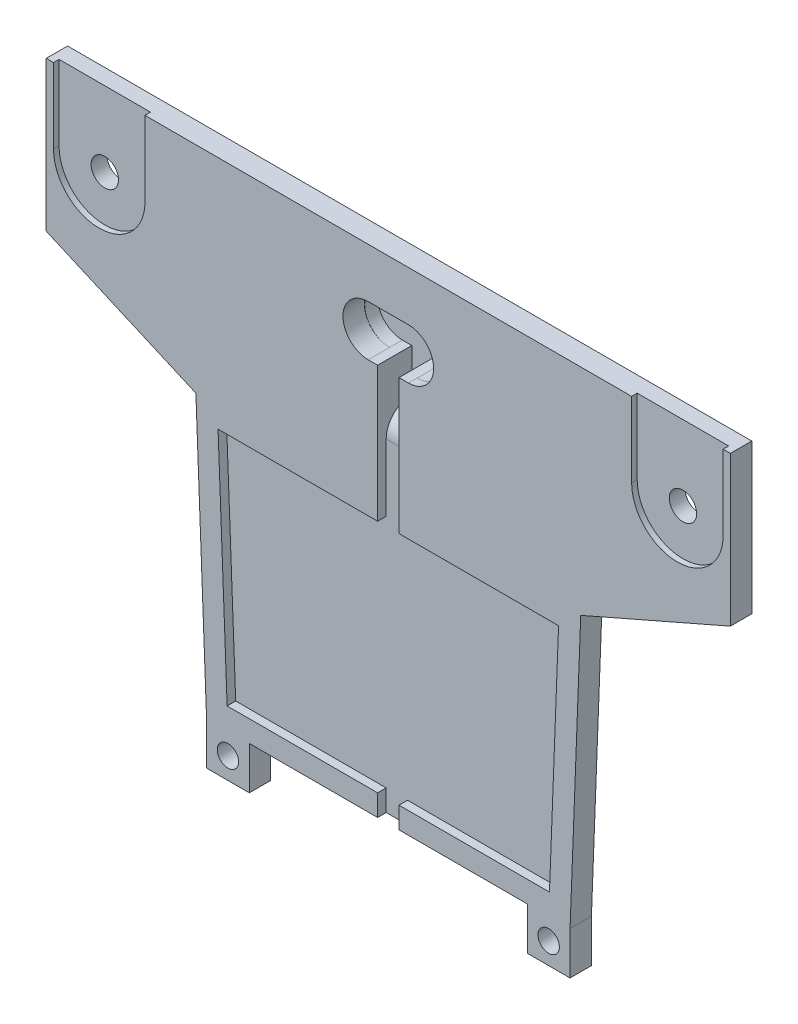
SolidWorks part; units mm, degrees
ref_plane "Front Plane" through (0, 0, 0) normal (0, 0, 1) x (1, 0, 0)
ref_plane "Top Plane" through (0, 0, 0) normal (0, 1, 0) x (1, 0, 0)
ref_plane "Right Plane" through (0, 0, 0) normal (1, 0, 0) x (0, 0, -1)
sketch "Sketch1" plane through (0, 0, 0) normal (0, 0, 1) x (1, 0, 0)
  line L0 (-53.975, 0) -> (53.975, 0)
  line L1 (53.975, 0) -> (57.15, 82.1613)
  line L2 (57.15, 82.1613) -> (101.6, 101.6)
  line L3 (101.6, 101.6) -> (101.6, 146.05)
  line L4 (101.6, 146.05) -> (-101.6, 146.05)
  line L5 (-101.6, 146.05) -> (-101.6, 101.6)
  line L6 (-101.6, 101.6) -> (-57.15, 82.1613)
  line L7 (-57.15, 82.1613) -> (-53.975, 0)
  point P4 (0, 0)
  point P5 (0, 0)
  point P11 (0, 146.05)
  dimension "D1" = 44.45
  dimension "D2" = 44.45
  dimension "D3" = 146.05
  dimension "D4" = 107.95
  dimension "D5" = 203.2
  dimension "D6" = 114.3
base flange "Main Body" sketch "Sketch1" thickness 6.35 reverse thickness direction no parameters "D1"=1
sketch "Sketch7" plane through (0, 0, 0) normal (0, 0, 1) x (1, 0, 0)
  line L0 (-50.5649, 76.2) -> (-47.8656, 6.35)
  line L1 (-47.8656, 6.35) -> (47.8656, 6.35)
  line L2 (47.8656, 6.35) -> (50.5649, 76.2)
  line L3 (50.5649, 76.2) -> (-50.5649, 76.2)
  line L4 (-57.15, 82.1613) -> (-53.975, 0) construction
  line L8 (-53.975, 0) -> (53.975, 0) construction
  line L9 (53.975, 0) -> (57.15, 82.1613) construction
  point P2 (0, 6.35)
  point P5 (0, 76.2)
  dimension "D1" = 6.35
  dimension "D2" = 6.35
  dimension "D3" = 69.85
  dimension "D4" = 6.35
extrude "Battery Spacing" cut sketch "Sketch7" against normal blind 2.54 normal cut yes
sketch "Sketch8" plane through (0, 0, 0) normal (0, 0, 1) x (1, 0, 0)
  line L0 (-5.969, 131.318) -> (5.969, 131.318)
  line L1 (5.969, 116.332) -> (-5.969, 116.332)
  line L3 (101.6, 146.05) -> (-101.6, 146.05) construction
  arc A0 (5.969, 131.318) -> (5.969, 116.332) centre (5.969, 123.825) cw
  arc A1 (-5.969, 116.332) -> (-5.969, 131.318) centre (-5.969, 123.825) cw
  circle A2 centre (85.852, 123.825) radius 4.064
  circle A3 centre (-85.852, 123.825) radius 4.064
  point P5 (1.524, 123.825)
  point P7 (-1.524, 123.825)
  point P8 (0, 131.318)
  point P9 (0, 116.332)
  point P12 (-13.462, 123.825)
  point P13 (13.462, 123.825)
  point P21 (0, 146.05)
  dimension "D1" = 26.924
  dimension "D2" = 72.39
  dimension "D3" = 72.39
  dimension "D4" = 14.732
  dimension "D5" = 11.938
extrude "Light Sockets" cut sketch "Sketch8" against normal blind 12.7 normal cut yes
sketch "Sketch9" plane through (0, 0, -6.35) normal (0, 0, -1) x (-1, 0, 0)
  line L0 (-9.525, 111.7653) -> (-9.525, 99.0653)
  line L1 (-9.525, 99.0653) -> (9.525, 99.0653)
  line L2 (9.525, 99.0653) -> (9.525, 111.7653)
  line L3 (9.525, 111.7653) -> (9.1017, 112.1697)
  line L4 (5.969, 136.398) -> (-5.969, 136.398)
  line L5 (-5.969, 111.252) -> (5.969, 111.252)
  line L6 (5.969, 136.398) -> (-5.969, 136.398)
  arc A4 (5.969, 111.252) -> (5.969, 136.398) centre (5.969, 123.825) ccw
  arc A5 (-5.969, 136.398) -> (-5.969, 111.252) centre (-5.969, 123.825) ccw
  arc A6 (9.525, 111.7653) -> (5.969, 136.398) centre (5.969, 123.825) ccw
  arc A7 (-5.969, 136.398) -> (-9.525, 111.7653) centre (-5.969, 123.825) ccw
  dimension "D2" = 19.05
  dimension "D3" = 12.7
  dimension "D4" = 12.7
  dimension "D1" = 5.08
extrude "Light Leads Pocket" add sketch "Sketch9" along normal blind 6.35
sketch "Sketch10" plane through (0, 0, 0) normal (0, 0, 1) x (1, 0, 0)
  line L0 (-3.175, 116.332) -> (3.175, 116.332)
  line L1 (-5.969, 116.332) -> (5.969, 116.332) construction
  line L2 (-5.969, 116.332) -> (5.969, 116.332) construction
  line L3 (3.175, 116.332) -> (3.175, 76.2)
  line L4 (50.5649, 76.2) -> (-50.5649, 76.2) construction
  line L5 (3.175, 76.2) -> (3.175, 6.35)
  line L6 (-47.8656, 6.35) -> (47.8656, 6.35) construction
  line L7 (3.175, 6.35) -> (3.175, 0)
  line L8 (-53.975, 0) -> (53.975, 0) construction
  line L9 (3.175, 0) -> (-3.175, 0)
  line L10 (-3.175, 0) -> (-3.175, 116.332)
  point P6 (0, 116.332)
  dimension "D1" = 6.35
extrude "Wire Trail" cut sketch "Sketch10" against normal blind 2.54 normal cut yes
sketch "Sketch12" plane through (0, 0, -2.54) normal (0, 0, 1) x (1, 0, 0)
  line L0 (-3.175, 116.332) -> (-5.9601, 116.332)
  line L1 (3.175, 116.332) -> (3.175, 103.7305)
  line L2 (3.175, 76.2) -> (3.175, 116.332) construction
  line L3 (3.175, 103.7305) -> (-3.175, 103.7305)
  line L4 (-3.175, 116.332) -> (-3.175, 76.2) construction
  line L5 (-3.175, 103.7305) -> (-3.175, 116.332)
  line L6 (-3.175, 116.332) -> (-3.175, 76.2) construction
  line L7 (3.175, 76.2) -> (3.175, 116.332) construction
  line L8 (-5.9601, 131.1354) -> (6.0002, 131.1354)
  line L9 (6.0002, 116.332) -> (3.175, 116.332)
  arc A0 (-5.9601, 116.332) -> (-5.9601, 131.1354) centre (-5.9601, 123.7337) cw
  arc A1 (6.0002, 131.1354) -> (6.0002, 116.332) centre (6.0002, 123.7337) cw
extrude "Lead Room" cut sketch "Sketch12" against normal blind 7.62 normal cut yes
fillet "Fillet1" radius 7.62 1 edges at (0, 103.7305, -2.54)
sketch "Sketch13" plane through (0, 0, 0) normal (0, 0, 1) x (1, 0, 0)
  line L0 (72.263, 146.05) -> (72.263, 123.825)
  line L1 (101.6, 146.05) -> (-101.6, 146.05) construction
  line L2 (99.441, 123.825) -> (99.441, 146.05)
  line L3 (99.441, 146.05) -> (72.263, 146.05)
  arc A0 (72.263, 123.825) -> (99.441, 123.825) centre (85.852, 123.825) ccw
  circle A1 centre (85.852, 123.825) radius 4.064 construction
  dimension "D1" = 27.178
extrude "Tab Slots" cut sketch "Sketch13" against normal blind 1.651 normal cut yes
mirror "Mirror1" about plane through (0, 0, 0) normal (1, 0, 0) of "Tab Slots"
sketch "Sketch14" plane through (0, 0, 0) normal (0, -1, 0) x (1, 0, 0)
  line L0 (3.175, 0) -> (53.975, 0) construction
  line L1 (41.275, 0) -> (53.975, 0)
  line L2 (41.275, 0) -> (41.275, -6.35)
  line L3 (41.275, -6.35) -> (53.975, -6.35)
  line L4 (53.975, 0) -> (53.975, -6.35)
  dimension "D1" = 12.7
extrude "Screw Mount" add sketch "Sketch14" along normal blind 12.7
mirror "Mirror2" about plane through (0, 0, 0) normal (1, 0, 0) of "Screw Mount"
sketch "Sketch15" plane through (0, 0, -6.35) normal (0, 0, -1) x (-1, 0, 0)
  line L0 (41.275, -12.7) -> (53.975, -12.7) construction
  line L1 (-41.275, -12.7) -> (-53.975, -12.7) construction
  line L2 (41.275, -12.7) -> (53.975, -12.7) construction
  line L3 (-41.275, -12.7) -> (-53.975, -12.7) construction
  line L4 (-41.275, -12.7) -> (-41.275, 0) construction
  line L5 (41.275, -12.7) -> (41.275, 0) construction
  line L6 (-41.275, -12.7) -> (-41.275, 0) construction
  line L7 (41.275, -12.7) -> (41.275, 0) construction
  line L8 (41.275, -6.35) -> (47.625, -6.35) construction
  line L9 (47.625, -6.35) -> (47.625, -12.7) construction
  line L10 (-41.275, -6.35) -> (-47.625, -6.35) construction
  line L11 (-47.625, -6.35) -> (-47.625, -12.7) construction
  circle A0 centre (47.625, -6.35) radius 3.175
  circle A1 centre (-47.625, -6.35) radius 3.175
  dimension "D1" = 6.35
extrude "Cut-Extrude1" cut sketch "Sketch15" against normal through all both and the other way through all normal cut yes
sketch "Bend-Lines1" [suppressed] plane through (0, 0, 0) normal (0, 1, 0) x (1, 0, 0)
sketch "Bounding-Box1" [suppressed] plane through (0, 0, 0) normal (0, 1, 0) x (1, 0, 0)
sheet metal parameters "Sheet-Metal1" thickness 6.35 parameters "D1"=1
flat pattern "Flat-Pattern1" [suppressed]
sketch "Bend-Lines2" plane through (0, 0, 0) normal (0, 1, 0) x (1, 0, 0)
sketch3d "Bounding-Box2" [suppressed]
  line L0 (101.6, 0, 0) -> (-101.6, 0, 0) construction
  line L1 (101.6, 146.05, 0) -> (-101.6, 146.05, 0) construction
  line L2 (101.6, 0, 0) -> (101.6, 146.05, 0) construction
  line L3 (-101.6, 0, 0) -> (-101.6, 146.05, 0) construction
sheet metal parameters "Sheet-Metal2" thickness 6.35 parameters "D1"=1
flat pattern "Flat-Pattern1"
sketch "Bend-Lines2" plane through (0, 0, 0) normal (0, 1, 0) x (1, 0, 0)
sketch3d "Bounding-Box2" [suppressed]
  line L0 (-101.6, 0, 0) -> (101.6, 0, 0) construction
  line L1 (-101.6, 146.05, 0) -> (101.6, 146.05, 0) construction
  line L2 (-101.6, 0, 0) -> (-101.6, 146.05, 0) construction
  line L3 (101.6, 0, 0) -> (101.6, 146.05, 0) construction
sheet metal parameters "Sheet-Metal3" thickness 6.35 parameters "D1"=1
flat pattern "Flat-Pattern1"
sketch "Bend-Lines2" plane through (0, 0, 0) normal (0, 1, 0) x (1, 0, 0)
sketch3d "Bounding-Box2" [suppressed]
  line L0 (-101.6, 0, 0) -> (101.6, 0, 0) construction
  line L1 (-101.6, 146.05, 0) -> (101.6, 146.05, 0) construction
  line L2 (-101.6, 0, 0) -> (-101.6, 146.05, 0) construction
  line L3 (101.6, 0, 0) -> (101.6, 146.05, 0) construction
sheet metal parameters "Sheet-Metal4" thickness 6.35 parameters "D1"=1
flat pattern "Flat-Pattern1"
sketch "Bend-Lines2" plane through (0, 0, 0) normal (0, 1, 0) x (1, 0, 0)
sketch3d "Bounding-Box2" [suppressed]
  line L0 (-101.6, 0, 0) -> (101.6, 0, 0) construction
  line L1 (-101.6, 146.05, 0) -> (101.6, 146.05, 0) construction
  line L2 (-101.6, 0, 0) -> (-101.6, 146.05, 0) construction
  line L3 (101.6, 0, 0) -> (101.6, 146.05, 0) construction
sheet metal parameters "Sheet-Metal5" thickness 6.35 parameters "D1"=1
flat pattern "Flat-Pattern1"
sketch "Bend-Lines2" plane through (0, 0, 0) normal (0, 1, 0) x (1, 0, 0)
sketch3d "Bounding-Box2" [suppressed]
  line L0 (-101.6, 0, 0) -> (101.6, 0, 0) construction
  line L1 (-101.6, 146.05, 0) -> (101.6, 146.05, 0) construction
  line L2 (-101.6, 0, 0) -> (-101.6, 146.05, 0) construction
  line L3 (101.6, 0, 0) -> (101.6, 146.05, 0) construction
sheet metal parameters "Sheet-Metal6" thickness 6.35 parameters "D1"=1
flat pattern "Flat-Pattern1"
sketch "Bend-Lines2" plane through (0, 0, 0) normal (0, 1, 0) x (1, 0, 0)
sketch3d "Bounding-Box2" [suppressed]
  line L0 (-101.6, 0, 0) -> (101.6, 0, 0) construction
  line L1 (-101.6, 146.05, 0) -> (101.6, 146.05, 0) construction
  line L2 (-101.6, 0, 0) -> (-101.6, 146.05, 0) construction
  line L3 (101.6, 0, 0) -> (101.6, 146.05, 0) construction
sheet metal parameters "Sheet-Metal7" thickness 6.35 parameters "D1"=1
flat pattern "Flat-Pattern1"
sketch "Bend-Lines2" plane through (0, 0, 0) normal (0, 1, 0) x (1, 0, 0)
sketch3d "Bounding-Box2" [suppressed]
  line L0 (-101.6, 0, 0) -> (101.6, 0, 0) construction
  line L1 (-101.6, 146.05, 0) -> (101.6, 146.05, 0) construction
  line L2 (-101.6, 0, 0) -> (-101.6, 146.05, 0) construction
  line L3 (101.6, 0, 0) -> (101.6, 146.05, 0) construction
sheet metal parameters "Sheet-Metal8" thickness 6.35 parameters "D1"=1
flat pattern "Flat-Pattern1"
sketch "Bend-Lines2" plane through (0, 0, 0) normal (0, 1, 0) x (1, 0, 0)
sketch3d "Bounding-Box2" [suppressed]
  line L0 (-101.6, 0, 0) -> (101.6, 0, 0) construction
  line L1 (-101.6, 146.05, 0) -> (101.6, 146.05, 0) construction
  line L2 (-101.6, 0, 0) -> (-101.6, 146.05, 0) construction
  line L3 (101.6, 0, 0) -> (101.6, 146.05, 0) construction
sheet metal parameters "Sheet-Metal9" thickness 6.35 parameters "D1"=1
flat pattern "Flat-Pattern1"
sketch "Bend-Lines2" plane through (0, 0, 0) normal (0, 1, 0) x (1, 0, 0)
sketch3d "Bounding-Box2" [suppressed]
  line L0 (-101.6, -10.16, 0) -> (101.6, -10.16, 0) construction
  line L1 (-101.6, 146.05, 0) -> (101.6, 146.05, 0) construction
  line L2 (-101.6, -10.16, 0) -> (-101.6, 146.05, 0) construction
  line L3 (101.6, -10.16, 0) -> (101.6, 146.05, 0) construction
sheet metal parameters "Sheet-Metal10" thickness 6.35 parameters "D1"=1
flat pattern "Flat-Pattern1"
sketch "Bend-Lines2" plane through (0, 0, 0) normal (0, 1, 0) x (1, 0, 0)
sketch3d "Bounding-Box2" [suppressed]
  line L0 (-101.6, -12.7, 0) -> (101.6, -12.7, 0) construction
  line L1 (-101.6, 146.05, 0) -> (101.6, 146.05, 0) construction
  line L2 (-101.6, -12.7, 0) -> (-101.6, 146.05, 0) construction
  line L3 (101.6, -12.7, 0) -> (101.6, 146.05, 0) construction
sheet metal parameters "Sheet-Metal11" thickness 6.35 parameters "D1"=1
flat pattern "Flat-Pattern1"
sketch "Bend-Lines2" plane through (0, 0, 0) normal (0, 1, 0) x (1, 0, 0)
sketch3d "Bounding-Box2" [suppressed]
  line L0 (-101.6, -12.7, 0) -> (101.6, -12.7, 0) construction
  line L1 (-101.6, 146.05, 0) -> (101.6, 146.05, 0) construction
  line L2 (-101.6, -12.7, 0) -> (-101.6, 146.05, 0) construction
  line L3 (101.6, -12.7, 0) -> (101.6, 146.05, 0) construction
